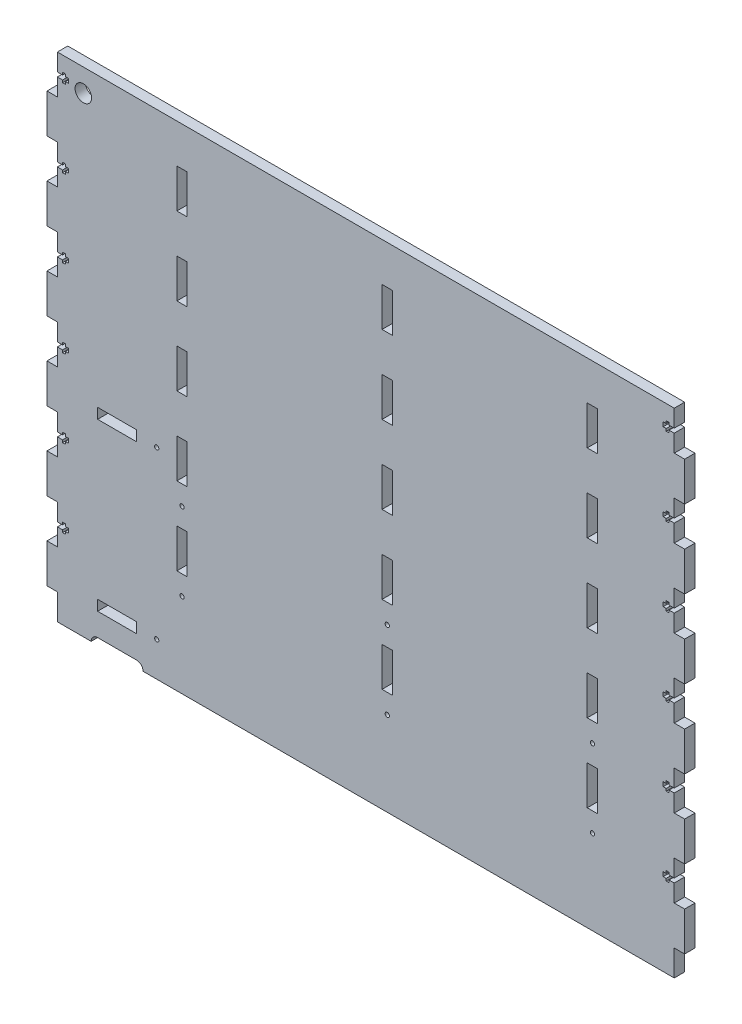
SolidWorks part; units mm, degrees
material "Acrylic (Medium-high impact)"
ref_plane "Front Plane" through (0, 0, 0) normal (0, 0, 1) x (1, 0, 0)
ref_plane "Top Plane" through (0, 0, 0) normal (0, 1, 0) x (1, 0, 0)
ref_plane "Right Plane" through (0, 0, 0) normal (1, 0, 0) x (0, 0, -1)
sketch "Sketch1" plane through (0, 0, 0) normal (0, 0, 1) x (1, 0, 0)
  line L0 (250, 350) -> (258, 350)
  line L1 (0, 0) -> (475, 0)
  line L2 (0, 380) -> (0, 0)
  line L3 (0, 380) -> (475, 380)
  line L4 (475, 0) -> (475, 380)
  line L5 (31, 158.5669) -> (61, 158.5669)
  line L6 (31, 158.5669) -> (31, 150.5669)
  line L7 (31, 150.5669) -> (61, 150.5669)
  line L8 (61, 158.5669) -> (61, 150.5669)
  line L9 (31, 30.5669) -> (61, 30.5669)
  line L10 (31, 30.5669) -> (31, 22.5669)
  line L11 (31, 22.5669) -> (61, 22.5669)
  line L12 (61, 30.5669) -> (61, 22.5669)
  line L13 (92, 350) -> (100, 350)
  line L14 (92, 350) -> (92, 320)
  line L15 (92, 320) -> (100, 320)
  line L16 (100, 350) -> (100, 320)
  line L17 (250, 350) -> (250, 320)
  line L18 (250, 320) -> (258, 320)
  line L19 (258, 350) -> (258, 320)
  line L20 (408, 350) -> (416, 350)
  line L21 (408, 350) -> (408, 320)
  line L22 (408, 320) -> (416, 320)
  line L23 (416, 350) -> (416, 320)
  line L24 (92, 290) -> (100, 290)
  line L25 (92, 290) -> (92, 260)
  line L26 (92, 260) -> (100, 260)
  line L27 (100, 290) -> (100, 260)
  line L28 (250, 290) -> (258, 290)
  line L29 (250, 290) -> (250, 260)
  line L30 (250, 260) -> (258, 260)
  line L31 (258, 290) -> (258, 260)
  line L32 (408, 290) -> (416, 290)
  line L33 (408, 290) -> (408, 260)
  line L34 (408, 260) -> (416, 260)
  line L35 (416, 290) -> (416, 260)
  line L36 (92, 230) -> (100, 230)
  line L37 (92, 230) -> (92, 200)
  line L38 (92, 200) -> (100, 200)
  line L39 (100, 230) -> (100, 200)
  line L40 (250, 230) -> (258, 230)
  line L41 (250, 230) -> (250, 200)
  line L42 (250, 200) -> (258, 200)
  line L43 (258, 230) -> (258, 200)
  line L44 (408, 230) -> (416, 230)
  line L45 (408, 230) -> (408, 200)
  line L46 (408, 200) -> (416, 200)
  line L47 (416, 230) -> (416, 200)
  line L48 (92, 170) -> (100, 170)
  line L49 (92, 170) -> (92, 140)
  line L50 (92, 140) -> (100, 140)
  line L51 (100, 170) -> (100, 140)
  line L52 (250, 170) -> (258, 170)
  line L53 (250, 170) -> (250, 140)
  line L54 (250, 140) -> (258, 140)
  line L55 (258, 170) -> (258, 140)
  line L56 (408, 170) -> (416, 170)
  line L57 (408, 170) -> (408, 140)
  line L58 (408, 140) -> (416, 140)
  line L59 (416, 170) -> (416, 140)
  line L60 (92, 110) -> (100, 110)
  line L61 (92, 110) -> (92, 80)
  line L62 (92, 80) -> (100, 80)
  line L63 (100, 110) -> (100, 80)
  line L64 (250, 110) -> (258, 110)
  line L65 (250, 110) -> (250, 80)
  line L66 (250, 80) -> (258, 80)
  line L67 (258, 110) -> (258, 80)
  line L68 (408, 110) -> (416, 110)
  line L69 (408, 110) -> (408, 80)
  line L70 (408, 80) -> (416, 80)
  line L71 (416, 110) -> (416, 80)
  line L146 (237.5, 0) -> (237.5, 380) construction
  circle A0 centre (20, 362.5) radius 6.35
  circle A1 centre (76.5, 154.5669) radius 1.65
  circle A2 centre (76.5, 26.5669) radius 1.65
  circle A3 centre (96, 125) radius 1.65
  circle A4 centre (254, 125) radius 1.65
  circle A5 centre (412, 125) radius 1.65
  circle A6 centre (96, 65) radius 1.65
  circle A7 centre (254, 65) radius 1.65
  circle A8 centre (412, 65) radius 1.65
  dimension "D4" = 5
  dimension "D6" = 92
  dimension "D3" = 3
  dimension "D5" = 30
  dimension "D9" = 15.5
  dimension "D10" = 3.3
  dimension "D12" = 3.3
  dimension "D13" = 12.7
  dimension "D1" = 475
  dimension "D2" = 380
  dimension "D7" = 30
  dimension "D8" = 8
  dimension "D11" = 15
  dimension "D14" = 17.5
  dimension "D15" = 20
extrude "Boss-Extrude1" add sketch "Sketch1" along normal blind 8
sketch "Sketch2" plane through (0, 0, 8) normal (0, 0, 1) x (1, 0, 0)
  line L0 (483, 350) -> (475, 350)
  line L1 (0, 350) -> (-8, 350)
  line L2 (0, 350) -> (0, 320)
  line L3 (0, 320) -> (-8, 320)
  line L4 (-8, 350) -> (-8, 320)
  line L5 (475, 380) -> (0, 380) construction
  line L6 (483, 350) -> (483, 320)
  line L7 (483, 320) -> (475, 320)
  line L8 (475, 350) -> (475, 320)
  line L9 (0, 290) -> (-8, 290)
  line L10 (0, 290) -> (0, 260)
  line L11 (0, 260) -> (-8, 260)
  line L12 (-8, 290) -> (-8, 260)
  line L13 (483, 290) -> (475, 290)
  line L14 (483, 290) -> (483, 260)
  line L15 (483, 260) -> (475, 260)
  line L16 (475, 290) -> (475, 260)
  line L17 (0, 230) -> (-8, 230)
  line L18 (0, 230) -> (0, 200)
  line L19 (0, 200) -> (-8, 200)
  line L20 (-8, 230) -> (-8, 200)
  line L21 (483, 230) -> (475, 230)
  line L22 (237.5, 380) -> (237.5, 0) construction
  line L23 (0, 0) -> (475, 0) construction
  line L24 (483, 230) -> (483, 200)
  line L25 (483, 200) -> (475, 200)
  line L26 (475, 230) -> (475, 200)
  line L27 (0, 170) -> (-8, 170)
  line L28 (0, 170) -> (0, 140)
  line L29 (0, 140) -> (-8, 140)
  line L30 (-8, 170) -> (-8, 140)
  line L31 (483, 170) -> (475, 170)
  line L32 (483, 170) -> (483, 140)
  line L33 (483, 140) -> (475, 140)
  line L34 (475, 170) -> (475, 140)
  line L35 (0, 110) -> (-8, 110)
  line L36 (0, 110) -> (0, 80)
  line L37 (0, 80) -> (-8, 80)
  line L38 (-8, 110) -> (-8, 80)
  line L39 (483, 110) -> (475, 110)
  line L40 (483, 110) -> (483, 80)
  line L41 (483, 80) -> (475, 80)
  line L42 (475, 110) -> (475, 80)
  line L43 (0, 50) -> (-8, 50)
  line L44 (0, 50) -> (0, 20)
  line L45 (0, 20) -> (-8, 20)
  line L46 (-8, 50) -> (-8, 20)
  line L47 (483, 50) -> (475, 50)
  line L48 (483, 50) -> (483, 20)
  line L49 (483, 20) -> (475, 20)
  line L50 (475, 50) -> (475, 20)
  dimension "D1" = 30
  dimension "D2" = 30
  dimension "D3" = 8
extrude "Boss-Extrude2" add sketch "Sketch2" against normal blind 8
sketch "Sketch4" plane through (0, 0, 8) normal (0, 0, 1) x (1, 0, 0)
  line L0 (475, 366.65) -> (471, 366.65)
  line L1 (0, 65) -> (8.5, 65) construction
  line L2 (471, 366.65) -> (471, 368.5)
  line L3 (471, 368.5) -> (468.8, 368.5)
  line L4 (468.8, 368.5) -> (468.8, 366.65)
  line L5 (468.8, 366.65) -> (466.5, 366.65)
  line L6 (475, 365) -> (466.5, 365) construction
  line L7 (466.5, 366.65) -> (466.5, 363.35)
  line L8 (468.8, 363.35) -> (466.5, 363.35)
  line L9 (468.8, 361.5) -> (468.8, 363.35)
  line L10 (471, 361.5) -> (468.8, 361.5)
  line L11 (471, 363.35) -> (471, 361.5)
  line L12 (475, 363.35) -> (471, 363.35)
  line L13 (475, 366.65) -> (475, 363.35)
  line L14 (0, 125) -> (8.5, 125) construction
  line L15 (0, 185) -> (8.5, 185) construction
  line L16 (0, 245) -> (8.5, 245) construction
  line L17 (0, 305) -> (8.5, 305) construction
  line L18 (0, 365) -> (8.5, 365) construction
  line L19 (0, 66.65) -> (0, 63.35)
  line L20 (0, 63.35) -> (4, 63.35)
  line L21 (4, 63.35) -> (4, 61.5)
  line L22 (4, 61.5) -> (6.2, 61.5)
  line L23 (6.2, 61.5) -> (6.2, 63.35)
  line L24 (6.2, 63.35) -> (8.5, 63.35)
  line L25 (8.5, 66.65) -> (8.5, 63.35)
  line L26 (6.2, 66.65) -> (8.5, 66.65)
  line L27 (6.2, 68.5) -> (6.2, 66.65)
  line L28 (4, 68.5) -> (6.2, 68.5)
  line L29 (4, 66.65) -> (4, 68.5)
  line L30 (0, 66.65) -> (4, 66.65)
  line L31 (0, 126.65) -> (0, 123.35)
  line L32 (0, 123.35) -> (4, 123.35)
  line L33 (4, 123.35) -> (4, 121.5)
  line L34 (4, 121.5) -> (6.2, 121.5)
  line L35 (6.2, 121.5) -> (6.2, 123.35)
  line L36 (6.2, 123.35) -> (8.5, 123.35)
  line L37 (8.5, 126.65) -> (8.5, 123.35)
  line L38 (6.2, 126.65) -> (8.5, 126.65)
  line L39 (6.2, 128.5) -> (6.2, 126.65)
  line L40 (4, 128.5) -> (6.2, 128.5)
  line L41 (4, 126.65) -> (4, 128.5)
  line L42 (0, 126.65) -> (4, 126.65)
  line L43 (0, 186.65) -> (0, 183.35)
  line L44 (0, 183.35) -> (4, 183.35)
  line L45 (4, 183.35) -> (4, 181.5)
  line L46 (4, 181.5) -> (6.2, 181.5)
  line L47 (6.2, 181.5) -> (6.2, 183.35)
  line L48 (6.2, 183.35) -> (8.5, 183.35)
  line L49 (8.5, 186.65) -> (8.5, 183.35)
  line L50 (6.2, 186.65) -> (8.5, 186.65)
  line L51 (6.2, 188.5) -> (6.2, 186.65)
  line L52 (4, 188.5) -> (6.2, 188.5)
  line L53 (4, 186.65) -> (4, 188.5)
  line L54 (0, 186.65) -> (4, 186.65)
  line L55 (0, 246.65) -> (0, 243.35)
  line L56 (0, 243.35) -> (4, 243.35)
  line L57 (4, 243.35) -> (4, 241.5)
  line L58 (4, 241.5) -> (6.2, 241.5)
  line L59 (6.2, 241.5) -> (6.2, 243.35)
  line L60 (6.2, 243.35) -> (8.5, 243.35)
  line L61 (8.5, 246.65) -> (8.5, 243.35)
  line L62 (6.2, 246.65) -> (8.5, 246.65)
  line L63 (6.2, 248.5) -> (6.2, 246.65)
  line L64 (4, 248.5) -> (6.2, 248.5)
  line L65 (4, 246.65) -> (4, 248.5)
  line L66 (0, 246.65) -> (4, 246.65)
  line L67 (0, 306.65) -> (0, 303.35)
  line L68 (0, 303.35) -> (4, 303.35)
  line L69 (4, 303.35) -> (4, 301.5)
  line L70 (4, 301.5) -> (6.2, 301.5)
  line L71 (6.2, 301.5) -> (6.2, 303.35)
  line L72 (6.2, 303.35) -> (8.5, 303.35)
  line L73 (8.5, 306.65) -> (8.5, 303.35)
  line L74 (237.5, 380) -> (237.5, 0) construction
  line L75 (6.2, 306.65) -> (8.5, 306.65)
  line L76 (6.2, 308.5) -> (6.2, 306.65)
  line L77 (4, 308.5) -> (6.2, 308.5)
  line L78 (4, 306.65) -> (4, 308.5)
  line L79 (0, 306.65) -> (4, 306.65)
  line L80 (0, 366.65) -> (0, 363.35)
  line L81 (0, 363.35) -> (4, 363.35)
  line L82 (4, 363.35) -> (4, 361.5)
  line L83 (4, 361.5) -> (6.2, 361.5)
  line L84 (6.2, 361.5) -> (6.2, 363.35)
  line L85 (6.2, 363.35) -> (8.5, 363.35)
  line L86 (8.5, 366.65) -> (8.5, 363.35)
  line L87 (6.2, 366.65) -> (8.5, 366.65)
  line L88 (6.2, 368.5) -> (6.2, 366.65)
  line L89 (4, 368.5) -> (6.2, 368.5)
  line L90 (4, 366.65) -> (4, 368.5)
  line L91 (0, 366.65) -> (4, 366.65)
  line L150 (475, 350) -> (475, 380) construction
  line L151 (475, 380) -> (0, 380) construction
  line L152 (0, 0) -> (475, 0) construction
  line L160 (31, 0) -> (61, 0) construction
  line L161 (31, 5) -> (61, 5)
  line L162 (31, -5) -> (61, -5)
  line L163 (475, 306.65) -> (471, 306.65)
  line L164 (471, 306.65) -> (471, 308.5)
  line L165 (471, 308.5) -> (468.8, 308.5)
  line L166 (468.8, 308.5) -> (468.8, 306.65)
  line L167 (468.8, 306.65) -> (466.5, 306.65)
  line L168 (466.5, 306.65) -> (466.5, 303.35)
  line L169 (468.8, 303.35) -> (466.5, 303.35)
  line L170 (468.8, 301.5) -> (468.8, 303.35)
  line L171 (471, 301.5) -> (468.8, 301.5)
  line L172 (471, 303.35) -> (471, 301.5)
  line L173 (475, 303.35) -> (471, 303.35)
  line L174 (475, 306.65) -> (475, 303.35)
  line L175 (475, 305) -> (466.5, 305) construction
  line L176 (475, 246.65) -> (471, 246.65)
  line L177 (471, 246.65) -> (471, 248.5)
  line L178 (471, 248.5) -> (468.8, 248.5)
  line L179 (468.8, 248.5) -> (468.8, 246.65)
  line L180 (468.8, 246.65) -> (466.5, 246.65)
  line L181 (466.5, 246.65) -> (466.5, 243.35)
  line L182 (468.8, 243.35) -> (466.5, 243.35)
  line L183 (468.8, 241.5) -> (468.8, 243.35)
  line L184 (471, 241.5) -> (468.8, 241.5)
  line L185 (471, 243.35) -> (471, 241.5)
  line L186 (475, 243.35) -> (471, 243.35)
  line L187 (475, 246.65) -> (475, 243.35)
  line L188 (475, 245) -> (466.5, 245) construction
  line L189 (475, 186.65) -> (471, 186.65)
  line L190 (471, 186.65) -> (471, 188.5)
  line L191 (471, 188.5) -> (468.8, 188.5)
  line L192 (468.8, 188.5) -> (468.8, 186.65)
  line L193 (468.8, 186.65) -> (466.5, 186.65)
  line L194 (466.5, 186.65) -> (466.5, 183.35)
  line L195 (468.8, 183.35) -> (466.5, 183.35)
  line L196 (468.8, 181.5) -> (468.8, 183.35)
  line L197 (471, 181.5) -> (468.8, 181.5)
  line L198 (471, 183.35) -> (471, 181.5)
  line L199 (475, 183.35) -> (471, 183.35)
  line L200 (475, 186.65) -> (475, 183.35)
  line L201 (475, 185) -> (466.5, 185) construction
  line L202 (475, 126.65) -> (471, 126.65)
  line L203 (471, 126.65) -> (471, 128.5)
  line L204 (471, 128.5) -> (468.8, 128.5)
  line L205 (468.8, 128.5) -> (468.8, 126.65)
  line L206 (468.8, 126.65) -> (466.5, 126.65)
  line L207 (466.5, 126.65) -> (466.5, 123.35)
  line L208 (468.8, 123.35) -> (466.5, 123.35)
  line L209 (468.8, 121.5) -> (468.8, 123.35)
  line L210 (471, 121.5) -> (468.8, 121.5)
  line L211 (471, 123.35) -> (471, 121.5)
  line L212 (475, 123.35) -> (471, 123.35)
  line L213 (475, 126.65) -> (475, 123.35)
  line L214 (475, 125) -> (466.5, 125) construction
  line L215 (475, 66.65) -> (471, 66.65)
  line L216 (471, 66.65) -> (471, 68.5)
  line L217 (471, 68.5) -> (468.8, 68.5)
  line L218 (468.8, 68.5) -> (468.8, 66.65)
  line L219 (468.8, 66.65) -> (466.5, 66.65)
  line L220 (466.5, 66.65) -> (466.5, 63.35)
  line L221 (468.8, 63.35) -> (466.5, 63.35)
  line L222 (468.8, 61.5) -> (468.8, 63.35)
  line L223 (471, 61.5) -> (468.8, 61.5)
  line L224 (471, 63.35) -> (471, 61.5)
  line L225 (475, 63.35) -> (471, 63.35)
  line L226 (475, 66.65) -> (475, 63.35)
  line L227 (475, 65) -> (466.5, 65) construction
  arc A0 (31, 5) -> (31, -5) centre (31, 0) ccw
  arc A1 (61, -5) -> (61, 5) centre (61, 0) ccw
  point P178 (46, 0)
  dimension "D1" = 5
  dimension "D2" = 2.2
  dimension "D3" = 4
  dimension "D4" = 2.3
  dimension "D5" = 7
  dimension "D7" = 3.3
  dimension "D6" = 6
extrude "Cut-Extrude2" cut sketch "Sketch4" against normal through all
